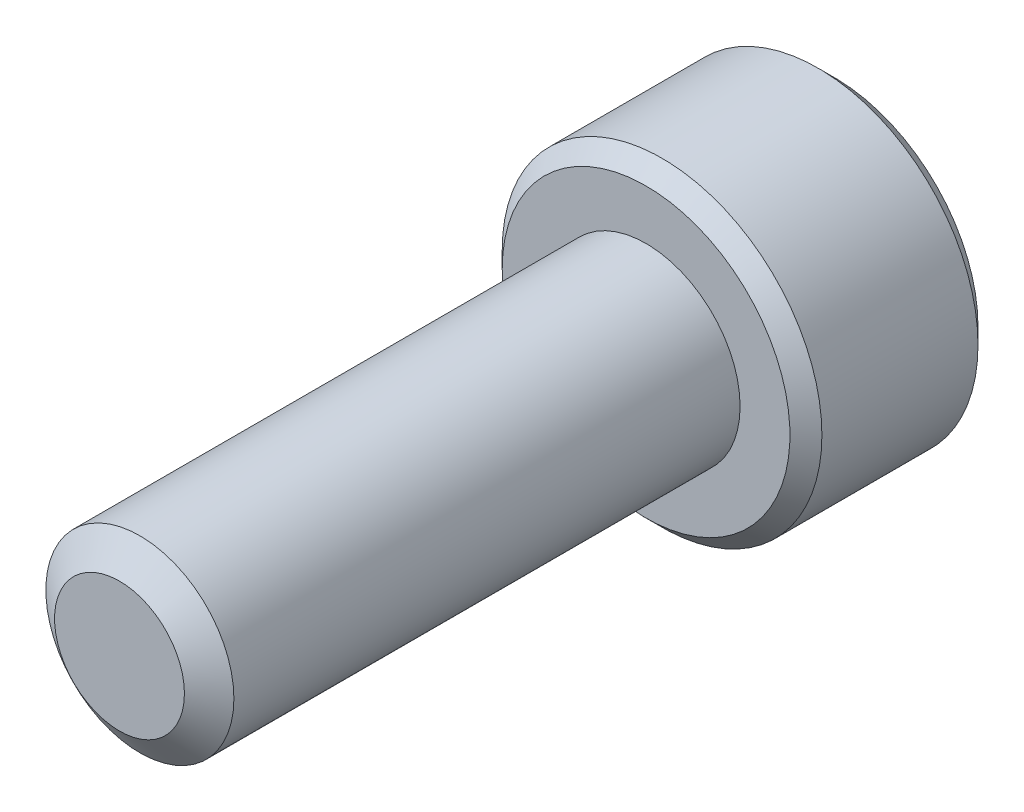
SolidWorks part; units mm, degrees
other "DetailItem1"
ref_plane "Front Plane" through (0, 0, 0) normal (0, 0, 1) x (1, 0, 0)
ref_plane "Top Plane" through (0, 0, 0) normal (0, 1, 0) x (1, 0, 0)
ref_plane "Right Plane" through (0, 0, 0) normal (1, 0, 0) x (0, 0, -1)
sketch "Sketch1" plane through (0, 0, 0) normal (0, 0, 1) x (1, 0, 0)
  circle A0 centre (0, 0) radius 2.5
  dimension "OD" = 5
extrude "Extrude1" add sketch "Sketch1" against normal blind 14
sketch "Sketch2" plane through (0, 0, 0) normal (0, 0, 1) x (1, 0, 0)
  circle A0 centre (0, 0) radius 2.5 construction
  circle A1 centre (0, 0) radius 2.5
curve "Helix/Spiral1" pitch 0.8 height 14.8 turns 18.5 parameters "pitch"=0.8
sketch "Sketch3" plane through (0, 0, 0) normal (1, 0, 0) x (0, 0, -1)
  line L0 (-0.7, 2.5) -> (-0.4, 1.9804)
  line L1 (-0.4, 1.9804) -> (-0.3, 1.9804)
  line L2 (-0.3, 1.9804) -> (0, 2.5)
  line L3 (-0.7, 2.5) -> (0, 2.5)
  line L4 (-0.35, 2.5) -> (-0.35, 1.9804) construction
  line L5 (-0.55, 2.2402) -> (-0.15, 2.2402) construction
  line L6 (0, 2.5) -> (0, -2.5) construction
  dimension "D1" = 0.1
  dimension "D2" = 0.4
  dimension "D3" = 60
sweep "Cut-Sweep1" [suppressed] cut profiles "Sketch3" path "Helix/Spiral1"
sketch "Sketch4" plane through (0, 0, 0) normal (1, 0, 0) x (0, 0, -1)
  line L0 (0.5417, 2.5) -> (0, 1.7264)
  line L1 (0, 1.7264) -> (0, 2.5)
  line L2 (0.5417, 2.5) -> (0, 2.5)
  line L3 (-0.7, 2.5) -> (0, 2.5) construction
  line L4 (0, 0) -> (7.0209, 0) construction
  dimension "D1" = 55
  dimension "D2" = 0.254
revolve "Cut-Revolve1" cut sketch "Sketch4" angle 360 about L4
sketch "Sketch6" plane through (0, 0, -14) normal (0, 0, -1) x (-1, 0, 0)
  circle A0 centre (0, 0) radius 4.25
  dimension "head dia" = 8.5
extrude "Extrude2" add sketch "Sketch6" along normal blind 5
sketch "Sketch7" plane through (0, 0, -19) normal (0, 0, -1) x (-1, 0, 0)
  line L1 (0, 2.3094) -> (-2, 1.1547)
  line L2 (-2, 1.1547) -> (-2, -1.1547)
  line L3 (-2, -1.1547) -> (0, -2.3094)
  line L4 (0, -2.3094) -> (2, -1.1547)
  line L5 (2, -1.1547) -> (2, 1.1547)
  line L6 (2, 1.1547) -> (0, 2.3094)
  circle A0 centre (0, 0) radius 2 construction
  dimension "hex dia" = 4
extrude "Cut-Extrude1" cut sketch "Sketch7" against normal blind 3
sketch "Sketch8" plane through (0, 0, -19) normal (0, 0, -1) x (-1, 0, 0)
  circle A0 centre (0, 0) radius 2.3094
extrude "Cut-Extrude2" cut sketch "Sketch8" against normal through all draft 45
chamfer "Chamfer1" distance 0.425 angle 45 2 edges at (-4.25, 0, -19) (-4.25, 0, -14)
sketch "Sketch10" plane through (0, 0, -14) normal (0, 0, 1) x (1, 0, 0)
  circle A1 centre (0, 0) radius 2.5
  circle A2 centre (0, 0) radius 2.5
  dimension "D1" = 0
ref_plane "Plane1" through (0, 0, 0) normal (0, 0, 1) x (1, 0, 0)
extrude "partial thread" [suppressed] add sketch "Sketch10" along normal up to surface (13 mm away) separate body up to plane "Plane1"
chamfer "Chamfer2" [suppressed] distance 0.1 angle 45
combine bodies "Combine1" [suppressed] operation type add bodies to combine 107 108
sketch "Sketch9" plane through (0, 0, 0) normal (1, 0, 0) x (0, 0, -1)
  line L0 (0, 2.5) -> (0, -2.5) construction
  line L1 (2, 2.5) -> (2, -2.5) construction
  dimension "D1" = 2
equation "\"D3@Helix/Spiral1\" = \"screw length@Extrude1\"+\"pitch@Helix/Spiral1\""
equation "\"D1@Sketch3\" = \"pitch@Helix/Spiral1\"*.125"
equation "\"D2@Sketch3\" = \"pitch@Helix/Spiral1\"*.5"
equation "\"D1@Cut-Extrude1\" = \"hex dia@Sketch7\"*.75"
equation "\"D1@Chamfer1\" = \"head dia@Sketch6\"*.05"
equation "\"D1@Sketch9\" = \"pitch@Helix/Spiral1\"*2.5"
equation "\"D1@Chamfer2\"=\"OD@Sketch1\"*.02"
